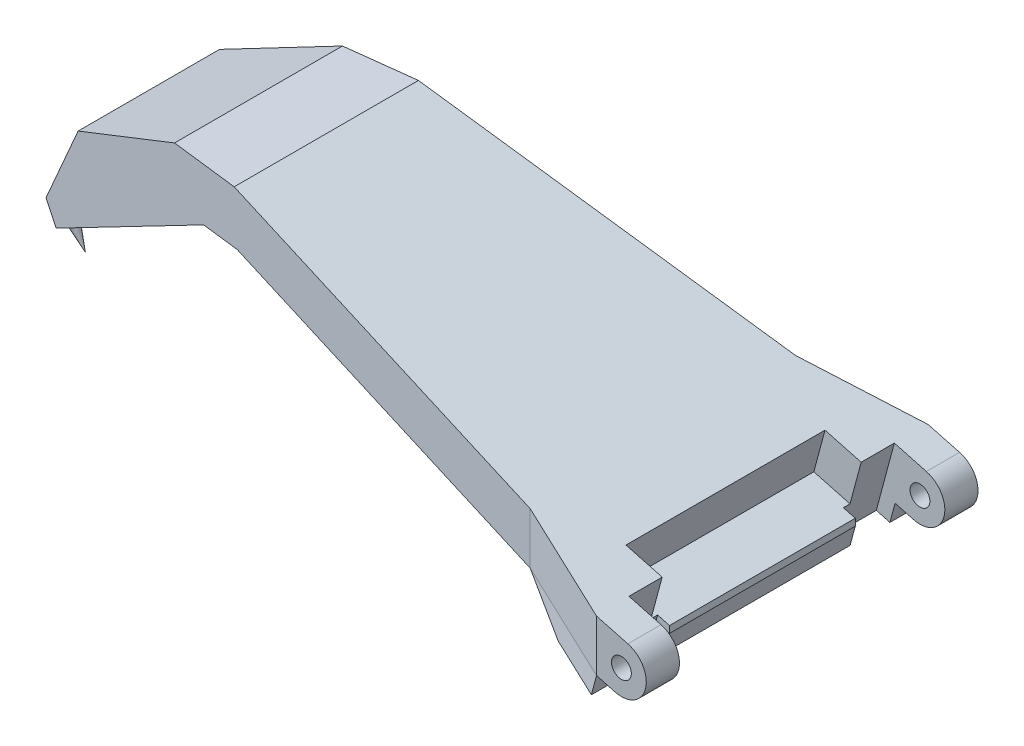
SolidWorks part; units mm, degrees
material "ABS"
ref_plane "Front Plane" through (0, 0, 0) normal (0, 0, 1) x (1, 0, 0)
ref_plane "Top Plane" through (0, 0, 0) normal (0, 1, 0) x (1, 0, 0)
ref_plane "Right Plane" through (0, 0, 0) normal (1, 0, 0) x (0, 0, -1)
sketch "Sketch3" plane through (0, 0, 0) normal (0, 0, 1) x (1, 0, 0)
  line L0 (0.9706, 3.6222) -> (-69.4823, 22.5)
  line L1 (-69.4823, 22.5) -> (-79.7011, 22.5)
  line L2 (-79.7011, 22.5) -> (-96.234, 14.7906)
  line L3 (-96.234, 14.7906) -> (-101.7321, 3)
  line L4 (-101.7321, 3) -> (-100, 0)
  line L5 (-100, 0) -> (-74.715, 14.5983)
  line L6 (-74.715, 14.5983) -> (-68.9706, 14.5983)
  line L7 (-68.9706, 14.5983) -> (-0.9706, -3.6222)
  line L8 (-0.9706, -3.6222) -> (0.9706, 3.6222) construction
  line L9 (-5.6356, -2.3722) -> (-3.6945, 4.8722) construction
  line L10 (-100, 0) -> (0, 0) construction
  circle A0 centre (0, 0) radius 1.5
  arc A2 (-0.9706, -3.6222) -> (0.9706, 3.6222) centre (0, 0) ccw
  point P14 (-5, 0)
  dimension "D2" = 3
  dimension "D1" = 100
  dimension "D3" = 7.5
  dimension "D4" = 68
  dimension "D5" = 30
  dimension "D6" = 15
  dimension "D7" = 125
  dimension "D8" = 5.498
  dimension "D9" = 3
  dimension "D10" = 155
  dimension "D11" = 22.5
sketch "start-width" plane through (0, 0, 0) normal (1, 0, 0) x (0, 0, -1)
  line L0 (-25, 0) -> (25, 0)
  point P4 (0, 0)
  dimension "D1" = 50
ref_plane "Plane1" through (-101.7321, 0, 0) normal (1, 0, 0) x (0, 0, -1)
sketch "end-width" plane through (-101.7321, 0, 0) normal (1, 0, 0) x (0, 0, -1)
  line L0 (10, 0) -> (-10, 0)
  point P4 (0, 0)
  dimension "D1" = 20
sketch "picture-background" plane through (0, 0, 0) normal (0, 0, 1) x (1, 0, 0)
  line L0 (-153.9208, -162.5929) -> (-22.7793, -162.5929) construction
extrude "Boss-Extrude2" add sketch "Sketch3" along direction (0, 0, -1) on the side against the normal up to vertex (25 mm away) and the other way up to vertex (25 mm away) up to point (0, 0, -25) other way up to point (0, 0, 25)
sketch "Sketch12" plane through (0, 0, 0) normal (0, 1, 0) x (1, 0, 0)
  line L0 (-101.7321, 10) -> (-101.7321, -10) construction
  line L1 (-101.7321, 10) -> (-3.75, 10) construction
  line L2 (-101.7321, 10) -> (-101.7321, -10)
  line L3 (-3.75, -25) -> (-3.75, 25)
  line L4 (-101.7321, 10) -> (-3.75, 25) construction
  line L5 (-101.7321, -10) -> (-3.75, -25) construction
  line L6 (-101.7321, 0) -> (0, 0) construction
  line L7 (0, -25) -> (0, 25) construction
  line L8 (0, -25) -> (0, 25) construction
  line L9 (-101.7321, 10) -> (-18.75, 20)
  line L10 (-18.75, 20) -> (-3.75, 25)
  line L11 (-18.75, -20) -> (-3.75, -25)
  line L12 (-101.7321, -10) -> (-18.75, -20)
  dimension "D1" = 3.75
  dimension "D2" = 20
  dimension "D3" = 15
extrude "top-form" cut sketch "Sketch12" along normal through all and the other way through all flip side to cut contours L2 L12 L11 L3 L10 L9 | L3 L10 L9 L2 L12 L11 region at (-46.1049, 0, 0)
sketch "Sketch13" plane through (0, 0, 0) normal (0, 0, 1) x (1, 0, 0)
  line L0 (-3.75, 4.8871) -> (-3.75, -2.8775) construction
  line L1 (-3.75, 4.8871) -> (-3.75, -2.8775)
  line L8 (0.9706, 3.6222) -> (-3.75, 4.8871)
  line L9 (-0.9706, -3.6222) -> (-3.75, -2.8775)
  arc A0 (-0.9706, -3.6222) -> (0.9706, 3.6222) centre (0, 0) ccw construction
  circle A1 centre (0, 0) radius 1.5 construction
  arc A2 (-0.9706, -3.6222) -> (0.9706, 3.6222) centre (0, 0) ccw
  circle A3 centre (0, 0) radius 1.5
extrude "end-extrude" add sketch "Sketch13" along direction (0, 0, 1) on the side of the normal up to vertex (25 mm away) and the other way up to vertex (25 mm away) up to point (-3.75, 4.8871, 25) other way up to point (-3.75, 4.8871, -25)
sketch "Sketch16" plane through (0.9706, 3.6222, 0) normal (0.2588, 0.9659, 0) x (0.9659, -0.2588, 0)
  line L0 (3.75, -25) -> (3.75, 25) construction
  line L1 (3.75, -25) -> (3.75, 25) construction
  line L2 (3.75, 25) -> (0, 25) construction
  line L3 (0, -25) -> (3.75, -25) construction
  line L4 (3.75, 25) -> (0, 25) construction
  line L5 (0, -25) -> (3.75, -25) construction
  line L6 (0, 25) -> (-4.8871, 25) construction
  line L7 (0, -25) -> (-4.8871, -25) construction
  line L8 (0, 25) -> (-4.8871, 25) construction
  line L9 (0, -25) -> (-4.8871, -25) construction
  line L10 (-4.8871, -25) -> (-4.8871, 25) construction
  line L11 (3.75, 0) -> (-4.8871, 0) construction
  line L14 (-4.8871, -20) -> (3.75, -20)
  line L15 (-4.8871, 20) -> (3.75, 20)
  line L16 (3.75, -20) -> (-4.8871, -20)
  line L17 (-4.8871, -20) -> (-4.8871, 0)
  line L18 (3.75, 0) -> (3.75, -20)
  line L19 (-4.8871, 20) -> (-4.8871, 0)
  line L20 (3.75, 0) -> (3.75, 20)
  line L21 (3.75, 0) -> (3.75, -20)
  line L22 (-4.8871, -20) -> (-4.8871, 0)
  point P8 (-4.8871, 0.0898)
  point P9 (-4.8871, -0.0904)
  point P11 (3.75, -0.0857)
  point P16 (3.75, 0.1493)
  point P17 (-4.8871, -0.0903)
  line M12 (0, -25) -> (0, 25)
  dimension "D1" = 40
extrude "spring_phalanx_place" cut sketch "Sketch16" along direction (0, -1, 0) on the side against the normal up to surface (7.5 mm away) contours L15 L19 L17 L14 M12 | L18 L20 L15 L14 M12 region at (-1.3897, 4.2547, 0) region at (2.7817, 3.1369, 0) up to face at (-23.1103, 2.3101, 0)
sketch "Sketch17" plane through (-25, 43.3013, 0) normal (0.5, -0.866, 0) x (0.866, 0.5, 0)
  line L0 (-86.6025, 0) -> (-57.4059, 0) construction
  line L1 (-86.6025, -10.2087) -> (-86.6025, 10.2087) construction
  line L2 (-57.4059, -13.2558) -> (-57.4059, 13.2558) construction
  line L3 (-86.6025, 10.2087) -> (-57.4059, 13.2558) construction
  circle A0 centre (-85.1025, 8.8571) radius 0.75
  circle A1 centre (-85.1025, -8.8571) radius 0.75
  dimension "D1" = 1.5
  dimension "D2" = 1.5
  dimension "D3" = 1.5
extrude "spikes" add sketch "Sketch17" along normal blind 6 draft 12
sketch "Sketch18" plane through (-0.9706, -3.6222, 0) normal (-0.2588, -0.9659, 0) x (0.9659, -0.2588, 0)
  line L0 (-18.4066, -20) -> (-2.8775, -25) construction
  line L2 (-18.4066, 20) -> (-2.8775, 25) construction
  line L4 (-2.8775, 25) -> (-2.8775, -25)
  line L5 (-18.4066, -20) -> (-18.4066, 20)
  line L7 (-18.4066, 20) -> (-2.8775, 25)
  line L8 (-18.4066, -20) -> (-2.8775, -25)
  line L9 (-2.8775, 25) -> (0, 25) construction
  line L10 (0, 25) -> (0, -25) construction
  line L11 (0, -25) -> (-2.8775, -25)
  line M4 (-2.8775, 25) -> (-18.4066, 20)
  line M8 (-18.4066, -20) -> (-2.8775, -25)
  line M12 (-2.8775, -20) -> (-2.8775, 20)
extrude "spring-support" add sketch "Sketch18" along normal blind 3 contours L5 L4 M8 M12 M4 region at (-10.9722, -0.9423, 0)
ref_plane "spring-cut-out-plane" through (-0.7118, -2.6563, 0) normal (0.2588, 0.9659, 0) x (0.9659, -0.2588, 0)
sketch "Sketch21" plane through (-0.7118, -2.6563, 0) normal (0.2588, 0.9659, 0) x (0.9659, -0.2588, 0)
  line L0 (-4.8871, 20) -> (0, 20) construction
  line L1 (-4.8871, 20) -> (0, 20)
  line L2 (0, 0) -> (-11, 0) construction
  line L3 (-4.8871, -20) -> (0, -20) construction
  line L4 (-4.8871, -20) -> (-5, -20)
  line L5 (-4.8871, -20) -> (0, -20)
  line L6 (0, 14) -> (-5, 14)
  line L8 (-5, -20) -> (-5, -14)
  line L12 (0, -14) -> (0, -20)
  line L13 (0, 14) -> (0, 20)
  line L16 (-4.8871, 20) -> (-5, 20)
  line L17 (-5, 20) -> (-5, 14)
  line L19 (0, -14) -> (-5, -14)
  dimension "D1" = 6
  dimension "D3" = 5
sketch "Sketch22" plane through (0, 0, 0) normal (0, 0, 1) x (1, 0, 0)
  line L0 (-19.5265, -1.756) -> (-18.75, 1.1418) construction
  line L1 (-19.5265, -1.756) -> (-18.75, 1.1418)
  line L3 (-19.5265, -1.756) -> (-4.5265, -5.7753) construction
  line L4 (-18.75, 1.1418) -> (-12.0265, -3.7656)
  line L5 (-12.0265, -3.7656) -> (-19.5265, -1.756)
  line L6 (-19.5265, -1.756) -> (-4.5265, -5.7753) construction
  line L7 (-18.75, 1.1418) -> (-3.75, -2.8775) construction
  line L8 (-3.75, -1.8422) -> (-10.9944, 0.0989)
  line L9 (-10.9944, 0.0989) -> (-9.3121, 6.3775)
  line L10 (-3.75, 4.8871) -> (-18.75, 8.9063) construction
  line L11 (-3.75, 4.8871) -> (-9.3121, 6.3775)
  line L12 (-3.75, 4.8871) -> (-3.75, -2.8775) construction
  line L13 (-3.75, 4.8871) -> (-3.75, -1.8422)
  line L14 (-18.75, 1.1418) -> (-3.75, -2.8775) construction
  line L15 (-3.75, 4.8871) -> (-3.75, -2.8775) construction
  point P11 (-9.8111, 2.597)
  point P12 (-10.75, 3.9304)
  point P13 (-10.75, 4.0153)
  point P15 (-10.75, 3.411)
  point P16 (0, 0)
  point P17 (-11.7356, 0.3422)
  point P18 (-10.9254, 6.8097)
  point P19 (-10.9098, 6.8014)
  point P20 (-14.8279, -2.8775)
  point P21 (-4.5579, -5.7668)
  point P23 (-14.5265, -3.0958)
  point P24 (-11.1625, 1.1418)
  point P25 (-11.408, 0.4195)
  point P26 (-8.3101, 6.109)
  point P27 (-9.0718, 6.3131)
  point P28 (-11.2015, 0.168)
  point P29 (-9.5586, 6.4435)
  dimension "D1" = 7.5
  dimension "D2" = 1
extrude "spring-support-corner-cut" cut sketch "Sketch22" against normal through all both and the other way through all contours L4 L5 L1
extrude "spring-place-cut" cut sketch "Sketch22<3>" along normal blind 15 and the other way blind 15 contours L13 L8 L9 L11
sketch "Sketch22<3>" plane through (0, 0, 0) normal (0, 0, 1) x (1, 0, 0) same geometry as "Sketch22"
extrude "phalanx-space-cut" cut sketch "Sketch21" against normal through all both and the other way through all
